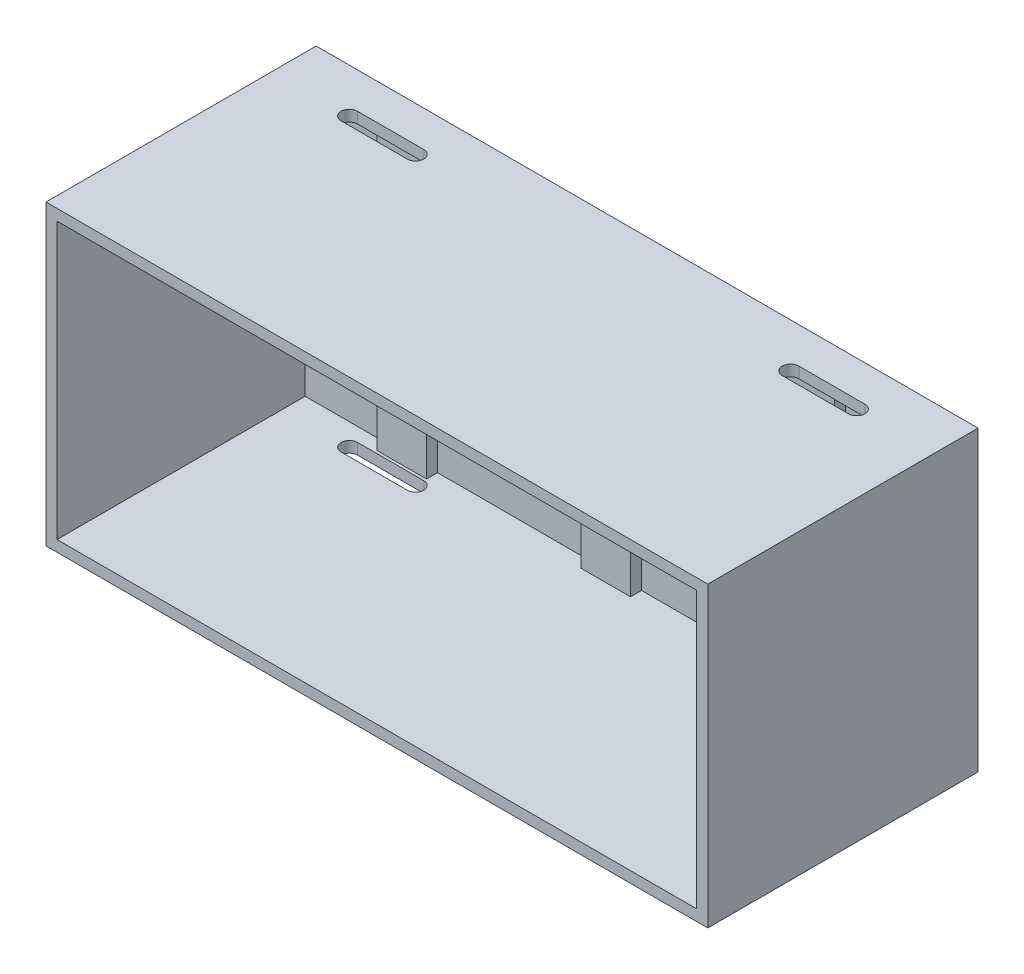
SolidWorks part; units mm, degrees
ref_plane "Front" through (0, 0, 0) normal (0, 0, 1) x (1, 0, 0)
ref_plane "Top" through (0, 0, 0) normal (0, 1, 0) x (1, 0, 0)
ref_plane "Right" through (0, 0, 0) normal (1, 0, 0) x (0, 0, -1)
sketch "Sketch1" plane through (0, 0, 0) normal (0, 0, 1) x (1, 0, 0)
  line L1 (-80.7473, 47) -> (39.2527, 47)
  line L2 (-80.7473, 47) -> (-80.7473, -7)
  line L3 (-80.7473, -7) -> (39.2527, -7)
  line L4 (39.2527, 47) -> (39.2527, -7)
  dimension "D1" = 54
  dimension "D2" = 120
extrude "Boss-Extrude1" add sketch "Sketch1" along normal blind 4 contours L1 L4 L3 L2
sketch "Sketch2" plane through (0, 0, 4) normal (0, 0, 1) x (1, 0, 0)
  line L1 (-80.7473, 47) -> (39.2527, 47)
  line L2 (-80.7473, 47) -> (-80.7473, -7)
  line L3 (-80.7473, -7) -> (39.2527, -7)
  line L4 (39.2527, 47) -> (39.2527, -7)
  line L5 (-78.7473, 45) -> (37.2527, 45)
  line L6 (-78.7473, 45) -> (-78.7473, -5)
  line L7 (-78.7473, -5) -> (37.2527, -5)
  line L8 (37.2527, 45) -> (37.2527, -5)
  dimension "D1" = 2
  dimension "D2" = 2
  dimension "D3" = 2
  dimension "D4" = 2
extrude "Boss-Extrude2" add sketch "Sketch2" along normal blind 45
sketch "Sketch3" plane through (0, 0, 4) normal (0, 0, 1) x (1, 0, 0)
  line L0 (37.2527, 45) -> (-78.7473, 45) construction
  line L1 (-63.7473, 45) -> (-54.7473, 45)
  line L2 (-63.7473, 45) -> (-63.7473, -5)
  line L3 (-63.7473, -5) -> (-54.7473, -5)
  line L4 (-54.7473, 45) -> (-54.7473, -5)
  line L5 (-78.7473, -5) -> (37.2527, -5) construction
  line L6 (-78.7473, -5) -> (37.2527, -5) construction
  line L7 (-26.7473, 45) -> (-17.7473, 45)
  line L8 (-26.7473, 45) -> (-26.7473, -5)
  line L9 (-26.7473, -5) -> (-17.7473, -5)
  line L10 (-17.7473, 45) -> (-17.7473, -5)
  line L11 (37.2527, 45) -> (-78.7473, 45) construction
  line L12 (10.2527, 45) -> (19.2527, 45)
  line L13 (10.2527, 45) -> (10.2527, -5)
  line L14 (10.2527, -5) -> (19.2527, -5)
  line L15 (19.2527, 45) -> (19.2527, -5)
  line L16 (37.2527, -5) -> (37.2527, 45) construction
  dimension "D1" = 9
  dimension "D2" = 9
  dimension "D3" = 9
  dimension "D4" = 18
  dimension "D5" = 28
  dimension "D6" = 28
extrude "Boss-Extrude3" add sketch "Sketch3" along normal blind 2
sketch "Sketch4" plane through (0, 0, 4) normal (0, 0, 1) x (1, 0, 0)
  line L2 (37.2527, 45) -> (-78.7473, 45) construction
  line L3 (37.2527, 45) -> (19.2527, 45) construction
  circle A0 centre (-4.7425, 39.5) radius 1.65
  circle A1 centre (-42.2054, 39.5) radius 1.65
  circle A3 centre (-72.6736, 39.5) radius 1.65
  circle A4 centre (29.2823, 39.5) radius 1.65
  point P12 (0, 0)
  dimension "D1" = 3.3
  dimension "D2" = 5.5
  dimension "D3" = 5.5
  dimension "D4" = 5.5
  dimension "D5" = 5.5
sketch "Sketch6" plane through (0, -7, 0) normal (0, -1, 0) x (-1, 0, 0)
  line L0 (66.7473, -8) -> (54.7473, -8) construction
  line L1 (66.7473, -9.5) -> (54.7473, -9.5)
  line L2 (66.7473, -6.5) -> (54.7473, -6.5)
  line L3 (-13.2527, -8) -> (-25.2527, -8) construction
  line L4 (-13.2527, -9.5) -> (-25.2527, -9.5)
  line L5 (-13.2527, -6.5) -> (-25.2527, -6.5)
  line L6 (80.7473, 0) -> (-39.2527, 0) construction
  line L7 (80.7473, -49) -> (80.7473, 0) construction
  line L8 (-39.2527, -49) -> (-39.2527, 0) construction
  arc A0 (66.7473, -9.5) -> (66.7473, -6.5) centre (66.7473, -8) ccw
  arc A1 (54.7473, -6.5) -> (54.7473, -9.5) centre (54.7473, -8) ccw
  arc A2 (-13.2527, -9.5) -> (-13.2527, -6.5) centre (-13.2527, -8) ccw
  arc A3 (-25.2527, -6.5) -> (-25.2527, -9.5) centre (-25.2527, -8) ccw
  point P2 (60.7473, -8)
  point P7 (-19.2527, -8)
  dimension "D1" = 12
  dimension "D2" = 12
  dimension "D3" = 8
  dimension "D4" = 3
  dimension "D5" = 3
  dimension "D6" = 20
  dimension "D7" = 20
extrude "Cut-Extrude3" cut sketch "Sketch6" against normal blind 14
sketch "Sketch7" plane through (0, 47, 0) normal (0, 1, 0) x (1, 0, 0)
  line L0 (13.2527, -9.5) -> (25.2527, -9.5) construction
  line L1 (25.2527, -6.5) -> (13.2527, -6.5) construction
  line L2 (-66.7473, -9.5) -> (-54.7473, -9.5) construction
  line L3 (-54.7473, -6.5) -> (-66.7473, -6.5) construction
  line L4 (13.2527, -9.5) -> (25.2527, -9.5)
  line L5 (25.2527, -6.5) -> (13.2527, -6.5)
  line L6 (-66.7473, -9.5) -> (-54.7473, -9.5)
  line L7 (-54.7473, -6.5) -> (-66.7473, -6.5)
  arc A0 (13.2527, -6.5) -> (13.2527, -9.5) centre (13.2527, -8) ccw construction
  arc A1 (25.2527, -9.5) -> (25.2527, -6.5) centre (25.2527, -8) ccw construction
  arc A2 (-54.7473, -9.5) -> (-54.7473, -6.5) centre (-54.7473, -8) ccw construction
  arc A3 (-66.7473, -6.5) -> (-66.7473, -9.5) centre (-66.7473, -8) ccw construction
  arc A4 (13.2527, -6.5) -> (13.2527, -9.5) centre (13.2527, -8) ccw
  arc A5 (25.2527, -9.5) -> (25.2527, -6.5) centre (25.2527, -8) ccw
  arc A6 (-54.7473, -9.5) -> (-54.7473, -6.5) centre (-54.7473, -8) ccw
  arc A7 (-66.7473, -6.5) -> (-66.7473, -9.5) centre (-66.7473, -8) ccw
extrude "Cut-Extrude4" cut sketch "Sketch7" against normal blind 14
extrude "Cut-Extrude5" cut sketch "Sketch4" against normal blind 14
